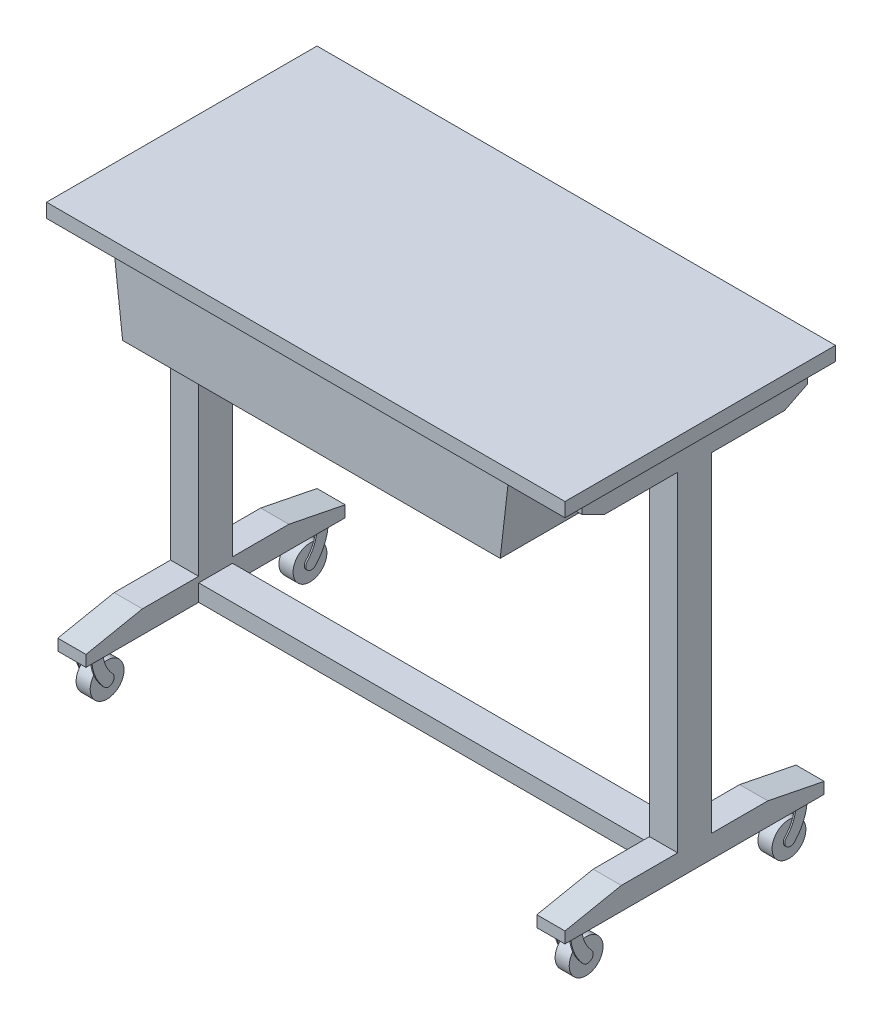
SolidWorks part; units mm, degrees
material "Plain Carbon Steel"
ref_plane "Front Plane" through (0, 0, 0) normal (0, 0, 1) x (1, 0, 0)
ref_plane "Top Plane" through (0, 0, 0) normal (0, 1, 0) x (1, 0, 0)
ref_plane "Right Plane" through (0, 0, 0) normal (1, 0, 0) x (0, 0, -1)
sketch "Sketch2" plane through (0, 0, 0) normal (0, 1, 0) x (1, 0, 0)
  line L1 (-584.2, -304.8) -> (584.2, -304.8)
  line L2 (-584.2, -304.8) -> (-584.2, 304.8)
  line L3 (-584.2, 304.8) -> (584.2, 304.8)
  line L4 (584.2, -304.8) -> (584.2, 304.8)
  line L5 (-584.2, -304.8) -> (584.2, 304.8) construction
  line L6 (-584.2, 304.8) -> (584.2, -304.8) construction
  point P0 (0, 0)
  dimension "D1" = 1168.4
  dimension "D2" = 609.6
extrude "Boss-Extrude1" add sketch "Sketch2" against normal blind 31.75
sketch "Sketch4" plane through (0, 0, 0) normal (0, 0, 1) x (1, 0, 0)
  line L0 (-584.2, -31.75) -> (584.2, -31.75) construction
  line L1 (-571.5, -31.75) -> (571.5, -31.75)
  line L2 (-571.5, -31.75) -> (-571.5, -82.55)
  line L3 (-571.5, -82.55) -> (571.5, -82.55)
  line L4 (571.5, -31.75) -> (571.5, -82.55)
  line L5 (584.2, -31.75) -> (584.2, 0) construction
  point P6 (0, -31.75)
  dimension "D1" = 12.7
  dimension "D2" = 50.8
extrude "Boss-Extrude2" add sketch "Sketch4" along normal mid plane 76.2 separate body
sketch "Sketch5" plane through (0, 0, 0) normal (0, 0, 1) x (1, 0, 0)
  line L0 (-444.5, -31.75) -> (444.5, -31.75)
  line L1 (444.5, -31.75) -> (425.45, -196.85)
  line L2 (425.45, -196.85) -> (-425.45, -196.85)
  line L3 (-425.45, -196.85) -> (-444.5, -31.75)
  line L4 (571.5, -31.75) -> (-571.5, -31.75) construction
  line L7 (-628.2169, -273.6924) -> (-77.5503, -273.6924) construction
  point P10 (0, -31.75)
  point P12 (0, -196.85)
  dimension "D2" = 165.1
  dimension "D3" = 850.9
  dimension "D4" = 889
extrude "Boss-Extrude3" add sketch "Sketch5" along normal offset from surface 12.7 and the other way offset from surface 444.5 up to face at (0, -15.875, 304.8) other way up to face at (0, -15.875, 304.8)
ref_plane "Plane1" through (0, -977.9, 0) normal (0, 1, 0) x (1, 0, 0)
sketch "Sketch6" plane through (571.5, 0, 0) normal (1, 0, 0) x (0, 0, -1)
  line L0 (-38.1, -825.5) -> (-165.1, -825.5)
  line L2 (-38.1, -825.5) -> (-38.1, -82.55)
  line L4 (38.1, -825.5) -> (38.1, -82.55)
  line L5 (165.1, -825.5) -> (38.1, -825.5)
  line L6 (292.1, -850.9) -> (292.1, -876.3)
  line L7 (292.1, -876.3) -> (-292.1, -876.3)
  line L8 (-292.1, -850.9) -> (-292.1, -876.3)
  line L10 (304.8, -31.75) -> (304.8, 0) construction
  line L11 (335.28, -977.9) -> (-335.28, -977.9) construction
  line L13 (38.1, -82.55) -> (203.2, -82.55)
  line L14 (-254, -31.75) -> (254, -31.75)
  line L15 (-254, -31.75) -> (-254, -57.15)
  line L16 (-203.2, -82.55) -> (-38.1, -82.55)
  line L17 (254, -31.75) -> (254, -57.15)
  line L18 (-304.8, -31.75) -> (304.8, -31.75) construction
  line L19 (-38.1, -82.55) -> (38.1, -82.55) construction
  line L20 (-38.1, -82.55) -> (-38.1, -31.75) construction
  line L21 (38.1, -82.55) -> (38.1, -31.75) construction
  line L22 (-254, -57.15) -> (-203.2, -82.55)
  line L23 (203.2, -82.55) -> (254, -57.15)
  line L24 (-292.1, -850.9) -> (-165.1, -825.5)
  line L25 (165.1, -825.5) -> (292.1, -850.9)
  point P10 (0, -876.3)
  point P17 (0, -31.75)
  dimension "D1" = 12.7
  dimension "D2" = 101.6
  dimension "D3" = 50.8
  dimension "D4" = 50.8
  dimension "D5" = 50.8
  dimension "D6" = 25.4
  dimension "D7" = 25.4
  dimension "D8" = 127
extrude "Boss-Extrude4" add sketch "Sketch6" against normal blind 63.5
mirror "Mirror1" about plane through (0, 0, 0) normal (1, 0, 0) of "Boss-Extrude4"
sketch "Sketch10" plane through (0, 0, 0) normal (1, 0, 0) x (0, 0, -1)
  line L1 (-38.1, -876.3) -> (38.1, -876.3)
  line L2 (-38.1, -876.3) -> (-38.1, -838.2)
  line L3 (-38.1, -838.2) -> (38.1, -838.2)
  line L4 (38.1, -876.3) -> (38.1, -838.2)
  line L5 (-292.1, -876.3) -> (292.1, -876.3) construction
  line L6 (38.1, -825.5) -> (38.1, -82.55) construction
  line L7 (-38.1, -82.55) -> (-38.1, -825.5) construction
  dimension "D1" = 38.1
extrude "Boss-Extrude7" add sketch "Sketch10" along normal up to surface and the other way up to surface up to face at (508, -692.15, 0) other way up to face at (-508, -692.15, 0)
ref_plane "Plane2" through (539.75, 0, 0) normal (1, 0, 0) x (0, 0, -1)
sketch "Sketch8" plane through (539.75, 0, 0) normal (1, 0, 0) x (0, 0, -1)
  line L0 (335.28, -977.9) -> (-335.28, -977.9) construction
  line L1 (-292.1, -850.9) -> (-292.1, -876.3) construction
  line L2 (292.1, -876.3) -> (292.1, -850.9) construction
  circle A0 centre (-228.6, -939.8) radius 38.1
  circle A1 centre (228.6, -939.8) radius 38.1
  dimension "D1" = 76.2
  dimension "D2" = 63.5
  dimension "D3" = 63.5
extrude "Boss-Extrude5" add sketch "Sketch8" along normal mid plane 31.75 separate body
sketch "Sketch9" plane through (555.625, 0, 0) normal (1, 0, 0) x (0, 0, -1)
  line L0 (-266.7, -876.3) -> (-241.3, -876.3)
  line L1 (-292.1, -876.3) -> (292.1, -876.3) construction
  line L2 (266.7, -876.3) -> (241.3, -876.3)
  line L3 (-241.3, -876.3) -> (241.3, -876.3) construction
  arc A0 (-241.3, -876.3) -> (-219.4034, -931.0414) centre (-161.925, -876.3) ccw
  arc A1 (-219.4034, -931.0414) -> (-237.7966, -948.5586) centre (-228.6, -939.8) cw
  arc A2 (-237.7966, -948.5586) -> (-266.7, -876.3) centre (-161.925, -876.3) cw
  circle A3 centre (-228.6, -939.8) radius 38.1 construction
  arc A4 (241.3, -876.3) -> (219.4034, -931.0414) centre (161.925, -876.3) cw
  arc A5 (219.4034, -931.0414) -> (237.7966, -948.5586) centre (228.6, -939.8) ccw
  arc A6 (237.7966, -948.5586) -> (266.7, -876.3) centre (161.925, -876.3) ccw
  circle A7 centre (228.6, -939.8) radius 38.1 construction
  point P21 (0, -876.3)
  point P24 (254, -876.3)
  dimension "D1" = 25.4
  dimension "D2" = 25.4
extrude "Boss-Extrude6" add sketch "Sketch9" along normal blind 3.175
mirror "Mirror2" about plane through (539.75, 0, 0) normal (1, 0, 0) of "Boss-Extrude6"
mirror "Mirror3" about plane through (0, 0, 0) normal (1, 0, 0) of bodies 110 111
